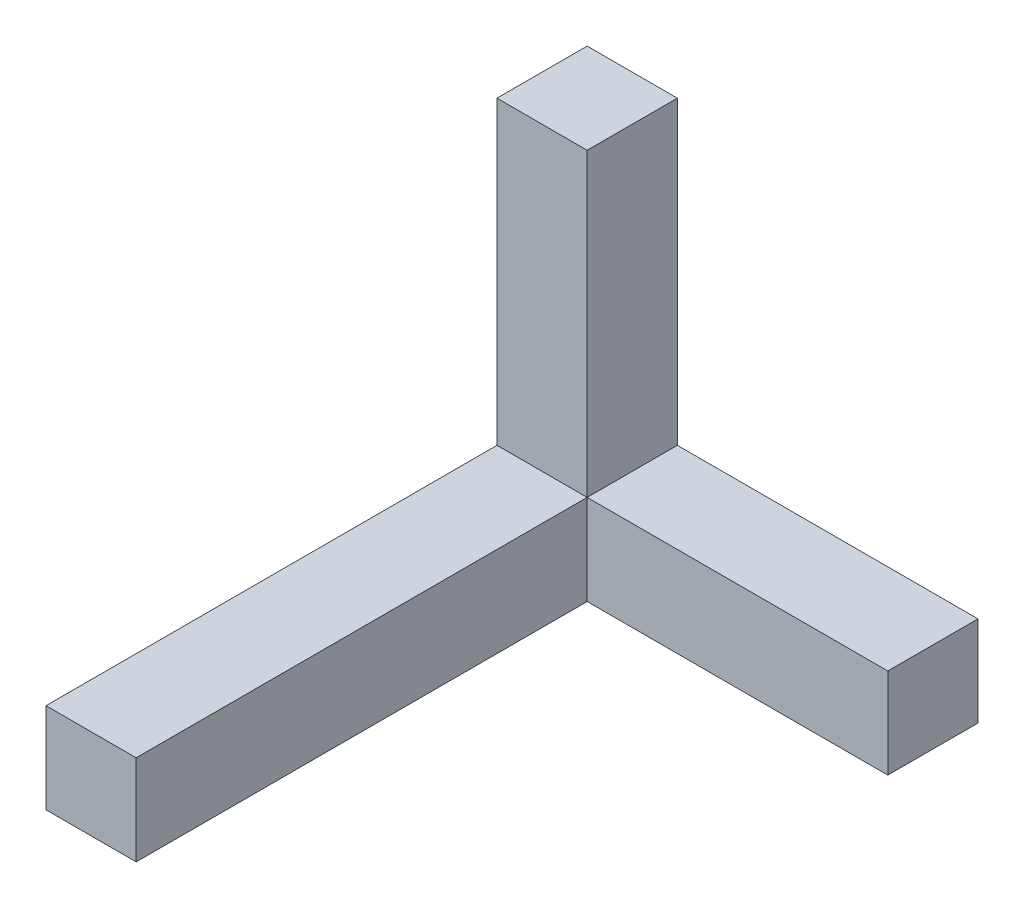
SolidWorks part; units mm, degrees
ref_plane "Front Plane" through (0, 0, 0) normal (0, 0, 1) x (1, 0, 0)
ref_plane "Top Plane" through (0, 0, 0) normal (0, 1, 0) x (1, 0, 0)
ref_plane "Right Plane" through (0, 0, 0) normal (1, 0, 0) x (0, 0, -1)
sketch "Sketch1" plane through (0, 0, 0) normal (0, 0, 1) x (1, 0, 0)
  line L5 (-1.5, -1.5) -> (1.5, -1.5)
  line L6 (-1.5, -1.5) -> (-1.5, 1.5)
  line L7 (-1.5, 1.5) -> (1.5, 1.5)
  line L8 (1.5, -1.5) -> (1.5, 1.5)
  line L9 (-1.5, -1.5) -> (1.5, 1.5) construction
  line L10 (-1.5, 1.5) -> (1.5, -1.5) construction
  point P0 (0, 0)
  dimension "D1" = 3
  dimension "D2" = 3
extrude "Boss-Extrude2" add sketch "Sketch1" along normal blind 15
sketch "Sketch2" plane through (1.5, 0, 0) normal (1, 0, 0) x (0, 0, -1)
  line L0 (-15, -1.5) -> (0, -1.5) construction
  line L1 (-15, 1.5) -> (-12, 1.5)
  line L2 (-15, 1.5) -> (-15, -1.5)
  line L3 (-15, -1.5) -> (-12, -1.5)
  line L4 (-12, 1.5) -> (-12, -1.5)
  dimension "D1" = 3
extrude "Boss-Extrude3" add sketch "Sketch2" along normal blind 10
sketch "Sketch3" plane through (0, 1.5, 0) normal (0, 1, 0) x (1, 0, 0)
  line L1 (1.5, -12) -> (-1.5, -12)
  line L2 (1.5, -12) -> (1.5, -15)
  line L3 (1.5, -15) -> (-1.5, -15)
  line L4 (-1.5, -12) -> (-1.5, -15)
extrude "Boss-Extrude4" add sketch "Sketch3" along normal blind 10
sketch "Sketch4" plane through (0, 0, 15) normal (0, 0, 1) x (1, 0, 0)
  line L1 (1.5, 1.5) -> (-1.5, 1.5)
  line L2 (1.5, 1.5) -> (1.5, -1.5)
  line L3 (1.5, -1.5) -> (-1.5, -1.5)
  line L4 (-1.5, 1.5) -> (-1.5, -1.5)
extrude "Boss-Extrude5" add sketch "Sketch4" along normal blind 15
extrude "Cut-Extrude1" cut sketch "Sketch1<2>" along normal blind 12
sketch "Sketch1<2>" plane through (0, 0, 0) normal (0, 0, 1) x (1, 0, 0) same geometry as "Sketch1"
